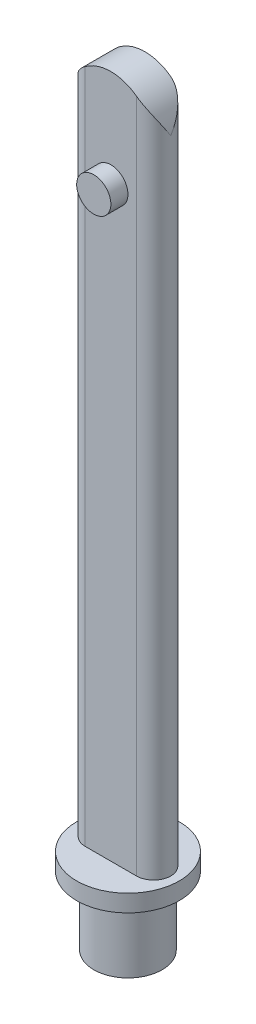
SolidWorks part; units mm, degrees
ref_plane "Front Plane" through (0, 0, 0) normal (0, 0, 1) x (1, 0, 0)
ref_plane "Top Plane" through (0, 0, 0) normal (0, 1, 0) x (1, 0, 0)
ref_plane "Right Plane" through (0, 0, 0) normal (1, 0, 0) x (0, 0, -1)
sketch "Sketch4" plane through (0, 0, 0) normal (0, 0, 1) x (1, 0, 0)
  line L0 (0, 0) -> (100, 0)
  line L2 (100, 200) -> (150, 200)
  line L4 (150, 250) -> (0, 250)
  line L5 (0, 250) -> (0, 0)
  line L6 (100, 200) -> (100, 0)
  line L7 (150, 250) -> (150, 200)
  dimension "D1" = 100
  dimension "D2" = 50
  dimension "D3" = 50
  dimension "D5" = 250
  dimension "D6" = 250
revolve "Revolve1" add sketch "Sketch4" angle 360 about L5 region at (56.8182, 134.0909, 0)
sketch "Sketch7" plane through (0, 250, 0) normal (0, 1, 0) x (1, 0, 0)
  line L1 (-75, 50) -> (75, 50)
  line L3 (-75, -50) -> (75, -50)
  arc A0 (-75, 50) -> (-75, -50) centre (-75, 0) ccw
  arc A1 (75, -50) -> (75, 50) centre (75, 0) ccw
  point P0 (0, 0)
  dimension "D3" = 100
  dimension "D4" = 100
  dimension "D1" = 150
  dimension "D2" = 100
  dimension "D5" = 75
  dimension "D6" = 50
extrude "Boss-Extrude1" add sketch "Sketch7" along normal blind 2000
sketch "Sketch8" plane through (0, 0, 50) normal (0, 0, 1) x (1, 0, 0)
  line L0 (125, 2250) -> (75, 2250) construction
  line L1 (-125, 2124.5) -> (-125, 2250)
  line L2 (-125, 2250) -> (125, 2250)
  line L3 (125, 2250) -> (125, 2124.5)
  arc A0 (125, 2124.5) -> (-125, 2124.5) centre (0, 2124.5) ccw
  point P1 (-125, 2250)
  dimension "D1" = 250
  dimension "D2" = 125.5
extrude "Cut-Extrude1" cut sketch "Sketch8" against normal blind 100
ref_axis "Link_1_Axis" through (0, 2213.8269, 0) along (0, -1, 0)
sketch "Sketch9" plane through (0, 0, 50) normal (0, 0, 1) x (1, 0, 0)
  line L0 (0, 2213.8269) -> (0, -260.6231) construction
  circle A0 centre (0, 1963.304) radius 50
extrude "Boss-Extrude2" add sketch "Sketch9" along normal blind 50
sketch "Sketch10" plane through (0, 0, 100) normal (0, 0, 1) x (1, 0, 0)
  line L5 (0, 1963.304) -> (0.9436, 1963.304)
  line L6 (0, 1963.304) -> (0, 1962.3477)
  line L7 (0, 1962.3477) -> (0.9436, 1962.3477)
  line L8 (0.9436, 1963.304) -> (0.9436, 1962.3477)
extrude "Cut-Extrude2" cut sketch "Sketch10" against normal blind 1
